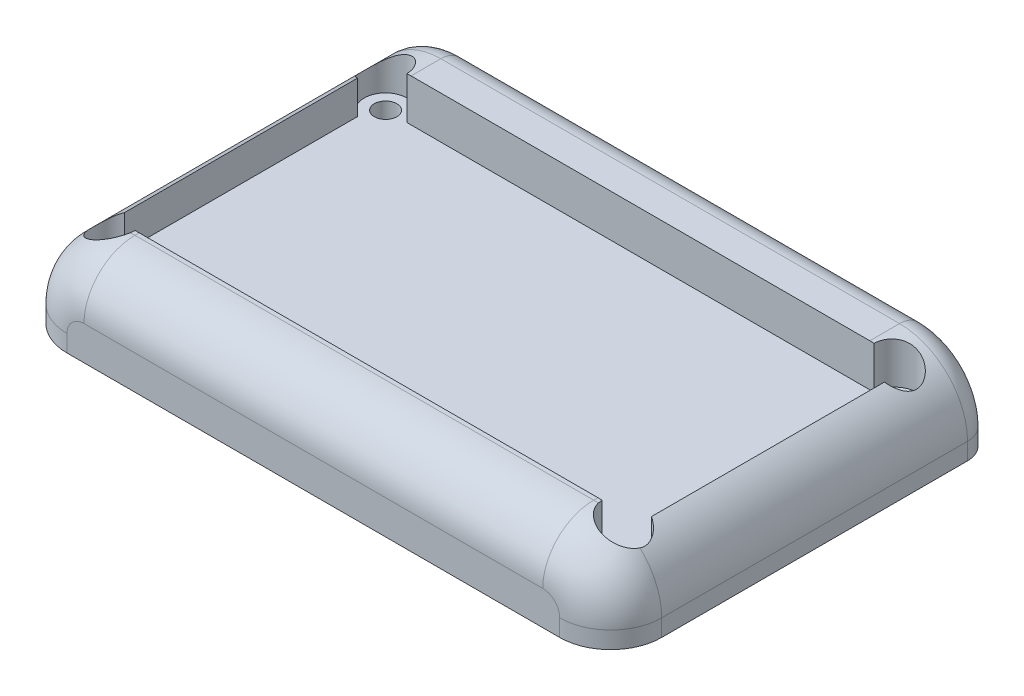
SolidWorks part; units mm, degrees
material "Markforged Onyx"
ref_plane "Front Plane" through (0, 0, 0) normal (0, 0, 1) x (1, 0, 0)
ref_plane "Top Plane" through (0, 0, 0) normal (0, 1, 0) x (1, 0, 0)
ref_plane "Right Plane" through (0, 0, 0) normal (1, 0, 0) x (0, 0, -1)
sketch "Sketch1" plane through (0, 0, 0) normal (0, 1, 0) x (1, 0, 0)
  line L1 (-88.9, -57.15) -> (88.9, -57.15)
  line L2 (-88.9, -57.15) -> (-88.9, 57.15)
  line L3 (-88.9, 57.15) -> (88.9, 57.15)
  line L4 (88.9, -57.15) -> (88.9, 57.15)
  line L5 (-88.9, -57.15) -> (88.9, 57.15) construction
  line L6 (-88.9, 57.15) -> (88.9, -57.15) construction
  point P0 (0, 0)
  dimension "7" = 177.8
  dimension "D2" = 114.3
extrude "Boss-Extrude1" add sketch "Sketch1" along normal blind 25.4
sketch "Sketch3" plane through (0, 25.4, 0) normal (0, 1, 0) x (1, 0, 0)
  line L0 (-88.9, 40.64) -> (88.9, 40.64) construction
  line L1 (-88.9, 57.15) -> (-88.9, -57.15) construction
  line L2 (88.9, -57.15) -> (88.9, 57.15) construction
  line L3 (88.9, 57.15) -> (-88.9, 57.15) construction
  line L4 (0, 57.15) -> (0, -57.15) construction
  line L5 (-88.9, -57.15) -> (88.9, -57.15) construction
  line L6 (88.9, 0) -> (-88.9, 0) construction
  circle A0 centre (-76.2, 40.64) radius 3.3782
  circle A1 centre (76.2, 40.64) radius 3.3782
  circle A2 centre (76.2, -40.64) radius 3.3782
  circle A3 centre (-76.2, -40.64) radius 3.3782
  circle A4 centre (76.2, 40.64) radius 6.35
  circle A5 centre (76.2, -40.64) radius 6.35
  circle A6 centre (-76.2, -40.64) radius 6.35
  circle A7 centre (-76.2, 40.64) radius 6.35
  dimension "D2" = 6.7564
  dimension "D1" = 16.51
  dimension "D3" = 12.7
  dimension "D4" = 2.9718
extrude "Cut-Extrude2" cut sketch "Sketch3" against normal through all contours A2 | A1 | A3 | A0 region at (76.2, 25.4, -40.64) region at (76.2, 25.4, 40.64) region at (-76.2, 25.4, 40.64)
sketch "Sketch4" plane through (0, 25.4, 0) normal (0, 1, 0) x (1, 0, 0)
  line L0 (78.74, 40.64) -> (78.74, -40.64)
  line L1 (76.2, 38.1) -> (-76.2, 38.1)
  line L2 (76.2, 38.1) -> (76.2, -38.1)
  line L3 (76.2, -38.1) -> (-76.2, -38.1)
  line L4 (-76.2, 38.1) -> (-76.2, -38.1)
  line L5 (76.2, 38.1) -> (-76.2, -38.1) construction
  line L6 (76.2, -38.1) -> (-76.2, 38.1) construction
  line L7 (78.74, -40.64) -> (-78.74, -40.64)
  line L8 (-78.74, 40.64) -> (-78.74, -40.64)
  line L9 (78.74, 40.64) -> (-78.74, 40.64)
  point P0 (0, 0)
  dimension "D1" = 152.4
  dimension "D2" = 76.2
  dimension "D3" = 2.54
extrude "Cut-Extrude3" cut sketch "Sketch4" against normal blind 12.7 contours L4 L3 L2 | L4 L2 | L1 L4 L2 | L0 L9 L8 L4 L1 L2 | L2 L0 | L8 L7 L0 L2 L3 L4 | L8 L4 region at (76.9678, 25.4, 0) region at (0, 25.4, 0)
extrude "Cut-Extrude4" cut sketch "Sketch3<3>" against normal blind 12.7
sketch "Sketch3<3>" plane through (0, 25.4, 0) normal (0, 1, 0) x (1, 0, 0) same geometry as "Sketch3"
fillet "Fillet4" radius 20.32 2 edges at (88.9, 25.4, 0) (-88.9, 25.4, 0)
fillet "Fillet7" radius 15.24 5 edges at (-88.9, 2.54, 57.15) (-82.9484, 19.4484, 57.15) (88.9, 2.54, 57.15) (82.9484, 19.4484, 57.15) (0, 25.4, 57.15)
fillet "Fillet8" radius 7.62 5 edges at (88.9, 2.54, -57.15) (82.9484, 19.4484, -57.15) (-88.9, 2.54, -57.15) (-82.9484, 19.4484, -57.15) (0, 25.4, -57.15)
